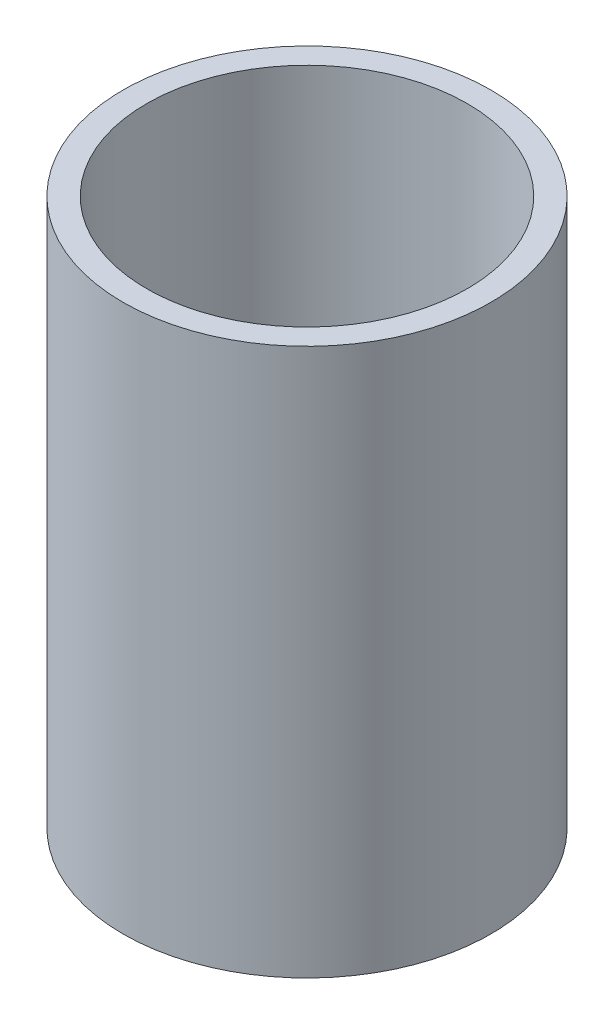
SolidWorks part; units mm, degrees
ref_plane "Front" through (0, 0, 0) normal (0, 0, 1) x (1, 0, 0)
ref_plane "Top" through (0, 0, 0) normal (0, 1, 0) x (1, 0, 0)
ref_plane "Right" through (0, 0, 0) normal (1, 0, 0) x (0, 0, -1)
sketch "Sketch2" plane through (0, 0, 0) normal (0, 1, 0) x (1, 0, 0)
  circle A0 centre (0, 0) radius 9.75
  circle A1 centre (0, 0) radius 8.5
  dimension "D1" = 17
  dimension "D2" = 19.5
extrude "Boss-Extrude1" add sketch "Sketch2" along normal blind 29
